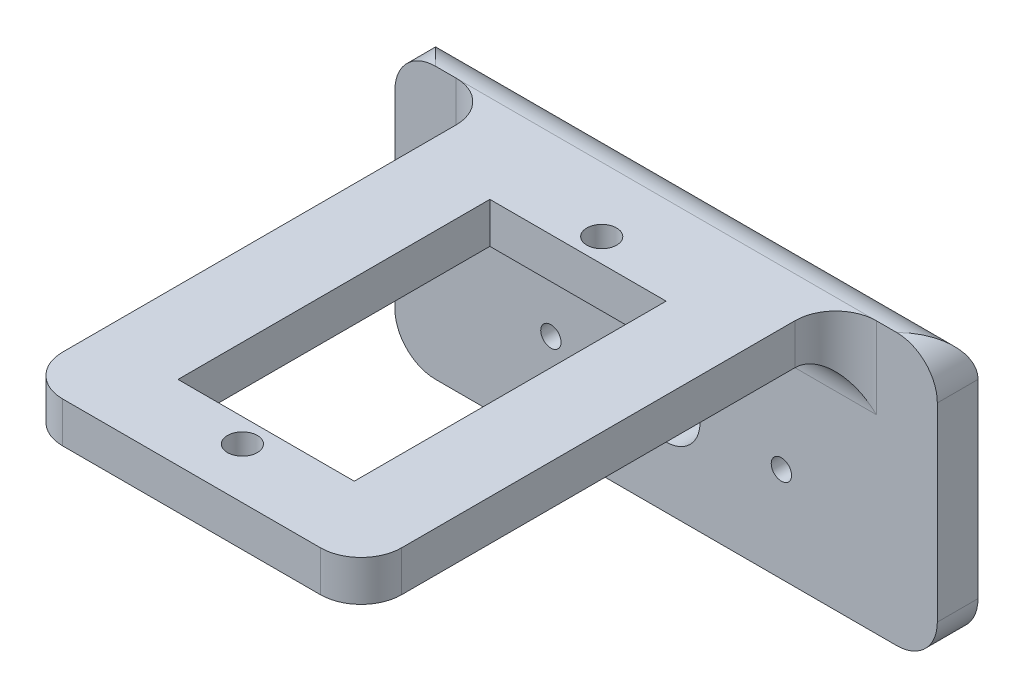
SolidWorks part; units mm, degrees
ref_plane "Plano frontal" through (0, 0, 0) normal (0, 0, 1) x (1, 0, 0)
ref_plane "Plano superior" through (0, 0, 0) normal (0, 1, 0) x (1, 0, 0)
ref_plane "Plano direito" through (0, 0, 0) normal (1, 0, 0) x (0, 0, -1)
sketch "Esboço1" plane through (0, 0, 0) normal (0, 0, 1) x (1, 0, 0)
  line L13 (-20, -12) -> (20, -12)
  line L14 (-20, -12) -> (-20, 8)
  line L15 (-20, 8) -> (20, 8)
  line L16 (20, -12) -> (20, 8)
  arc A12 (-2.4269, 0.6) -> (-2.4269, -0.6) centre (0, 0) ccw
  point P29 (0, 8)
  dimension "D8" = 5
  dimension "D3" = 20
  dimension "D4" = 40
  dimension "D5" = 12
extrude "Ressalto-extrusão1" add sketch "Esboço1" against normal blind 1 contours L13 L16 L15 L14 region at (0, -2, 0)
sketch "Esboço2" plane through (0, 0, 0) normal (0, 0, 1) x (1, 0, 0)
  line L0 (-20, 8) -> (20, 8) construction
  circle A0 centre (0, -5) radius 2.5
  circle A4 centre (-8.5, -5) radius 0.75
  dimension "D1" = 13
  dimension "D2" = 5
  dimension "D3" = 1.5
  dimension "D4" = 8.5
sketch "Esboço3" plane through (0, 0, 0) normal (0, 0, 1) x (1, 0, 0)
  line L1 (-20, -12) -> (20, -12)
  line L2 (-20, -12) -> (-20, 8)
  line L3 (-20, 8) -> (20, 8)
  line L4 (20, -12) -> (20, 8)
extrude "Ressalto-extrusão2" add sketch "Esboço3" along normal blind 2
extrude "Corte-extrusão1" cut sketch "Esboço2" along normal up to surface and the other way up to surface up to face at (0, -2, 2) other way up to face at (0, -2, -1)
sketch "Esboço4" plane through (0, 8, 0) normal (0, 1, 0) x (1, 0, 0)
  line L0 (20, -2) -> (-20, -2) construction
  line L1 (6.5, -31.5) -> (-6.5, -31.5)
  line L2 (6.5, -31.5) -> (6.5, -8.5)
  line L3 (6.5, -8.5) -> (-6.5, -8.5)
  line L4 (-6.5, -31.5) -> (-6.5, -8.5)
  line L5 (-20, 1) -> (20, 1) construction
  line L6 (12.5, -2) -> (-12.5, -2)
  line L7 (12.5, -2) -> (12.5, -37)
  line L8 (12.5, -37) -> (-12.5, -37)
  line L9 (-12.5, -2) -> (-12.5, -37)
  line L10 (-12.5, -2) -> (12.5, -2)
  line L11 (-12.5, -2) -> (-12.5, 1)
  line L12 (-12.5, 1) -> (12.5, 1)
  line L13 (12.5, -2) -> (12.5, 1)
  circle A0 centre (0, -6.75) radius 1.1
  circle A1 centre (0, -33.25) radius 1.1
  point P6 (0, -31.5)
  point P13 (0, -2)
  point P14 (0, -37)
  line M5 (-20, -2) -> (20, -2)
  line M7 (20, 1) -> (-20, 1)
  dimension "D6" = 4.75
  dimension "D7" = 2.2
  dimension "D8" = 26.5
  dimension "D1" = 6.5
  dimension "D2" = 23
  dimension "D3" = 13
  dimension "D4" = 25
  dimension "D5" = 35
extrude "Ressalto-extrusão3" add sketch "Esboço4" against normal blind 3 contours L13 L11 M5 M7 | L9 L8 L7 L1 L4 L3 L2 M5 region at (12.0699, 8, 19.5) region at (0, 8, 0.5)
mirror "Mirror1" about plane through (0, 0, 0) normal (1, 0, 0) of "Corte-extrusão1"
fillet "Fillet2" radius 3 10 edges at (0, 8, -1) (20, 8, 0.5) (20, -12, 0.5) (-20, -12, 0.5) (-20, 8, 0.5) (12.5, 6.5, 37) (-12.5, 6.5, 37) (12.5, 6.5, 2) (0, 5, 2) (-12.5, 6.5, 2)
